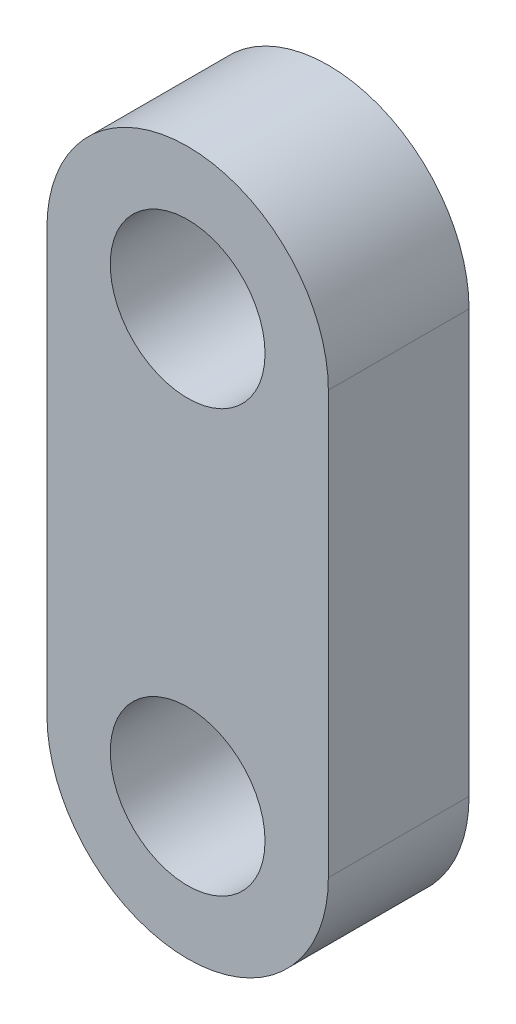
SolidWorks part; units mm, degrees
material "ABS"
ref_plane "Front Plane" through (0, 0, 0) normal (0, 0, 1) x (1, 0, 0)
ref_plane "Top Plane" through (0, 0, 0) normal (0, 1, 0) x (1, 0, 0)
ref_plane "Right Plane" through (0, 0, 0) normal (1, 0, 0) x (0, 0, -1)
ref_axis "X" through (-88.99, 0, 0) along (1, 0, 0)
ref_axis "Y" through (0, 55, 0) along (0, -1, 0)
ref_axis "Z" through (0, 0, -88.99) along (0, 0, 1)
sketch "Sketch1" plane through (0, 0, 0) normal (0, 0, 1) x (1, 0, 0)
  line L0 (0, 7.5) -> (0, -7.5) construction
  line L2 (5, 7.5) -> (5, -7.5)
  line L3 (-5, 7.5) -> (-5, -7.5)
  arc A0 (5, 7.5) -> (-5, 7.5) centre (0, 7.5) ccw
  arc A1 (-5, -7.5) -> (5, -7.5) centre (0, -7.5) ccw
  circle A2 centre (0, 7.5) radius 2.5 construction
  circle A3 centre (0, -7.5) radius 2.5 construction
  point P5 (0, 0)
  dimension "D2" = 5
  dimension "D3" = 2.5
  dimension "D1" = 15
extrude "Boss-Extrude1" add sketch "Sketch1" along normal blind 5
sketch "Sketch4" plane through (0, 0, 5) normal (0, 0, 1) x (1, 0, 0)
  point P0 (0, 7.5)
  point P3 (0, -7.5)
hole_wizard "M5 Clearance Hole1" positions "Sketch4" profile "Sketch3" hole size "M5" standard "ANSI Metric" end condition through all
sketch "Sketch3" plane through (0, 7.5, 5) normal (1, 0, 0) x (0, -1, 0)
  line L0 (0, 0) -> (0, 5)
  line L1 (0, 5) -> (2.75, 5)
  line L2 (2.75, 5) -> (2.75, 0)
  line L5 (2.75, 0) -> (0, 0)
  line L11 (0, -6.35) -> (0, 107.95) construction
  dimension "Thru Hole Dia." = 5.5
  dimension "Thru Hole Depth" = 5
